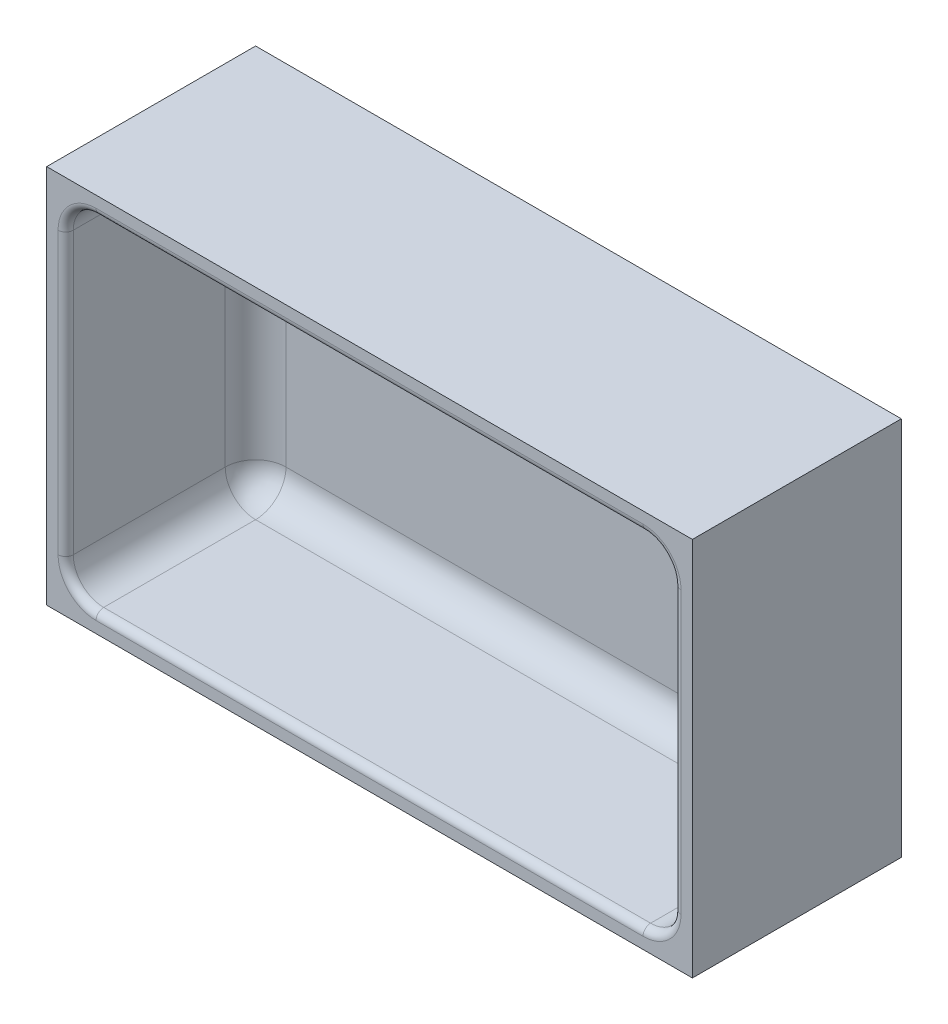
SolidWorks part; units mm, degrees
ref_plane "Ön Düzlem" through (0, 0, 0) normal (1, 0, 0) x (0, 1, 0)
ref_plane "Üst Düzlem" through (0, 0, 0) normal (0, 0, 1) x (0, 1, 0)
ref_plane "Sağ Düzlem" through (0, 0, 0) normal (0, 1, 0) x (-1, 0, 0)
sketch "Çizim1" plane through (0, 0, 0) normal (0, 0, 1) x (0, 1, 0)
  line L0 (0, 0) -> (100, 0)
  line L1 (0, 0) -> (0, 170)
  line L2 (0, 170) -> (100, 170)
  line L3 (100, 170) -> (100, 0)
  line L4 (5, 5) -> (5, 165)
  line L5 (5, 165) -> (95, 165)
  line L6 (95, 165) -> (95, 5)
  line L7 (5, 5) -> (95, 5)
  dimension "D1" = 5
extrude "Yükseklik-Ekstrüzyon1" add sketch "Çizim1" along normal blind 5 contours L4 L5 L6 L7
extrude "Yükseklik-Ekstrüzyon2" add sketch "Çizim1<3>" along normal blind 55
sketch "Çizim1<3>" plane through (0, 0, 0) normal (0, 0, 1) x (0, 1, 0) same geometry as "Çizim1"
fillet "Radyus1" radius 8 8 edges at (-5, 95, 30) (-5, 5, 30) (-165, 95, 30) (-165, 5, 30) (-165, 50, 5) (-5, 50, 5) (-85, 95, 5) (-85, 5, 5)
fillet "Radyus2" radius 2 8 edges at (-162.6569, 7.3431, 55) (-165, 50, 55) (-162.6569, 92.6569, 55) (-85, 95, 55) (-7.3431, 92.6569, 55) (-5, 50, 55) (-7.3431, 7.3431, 55) (-85, 5, 55)
